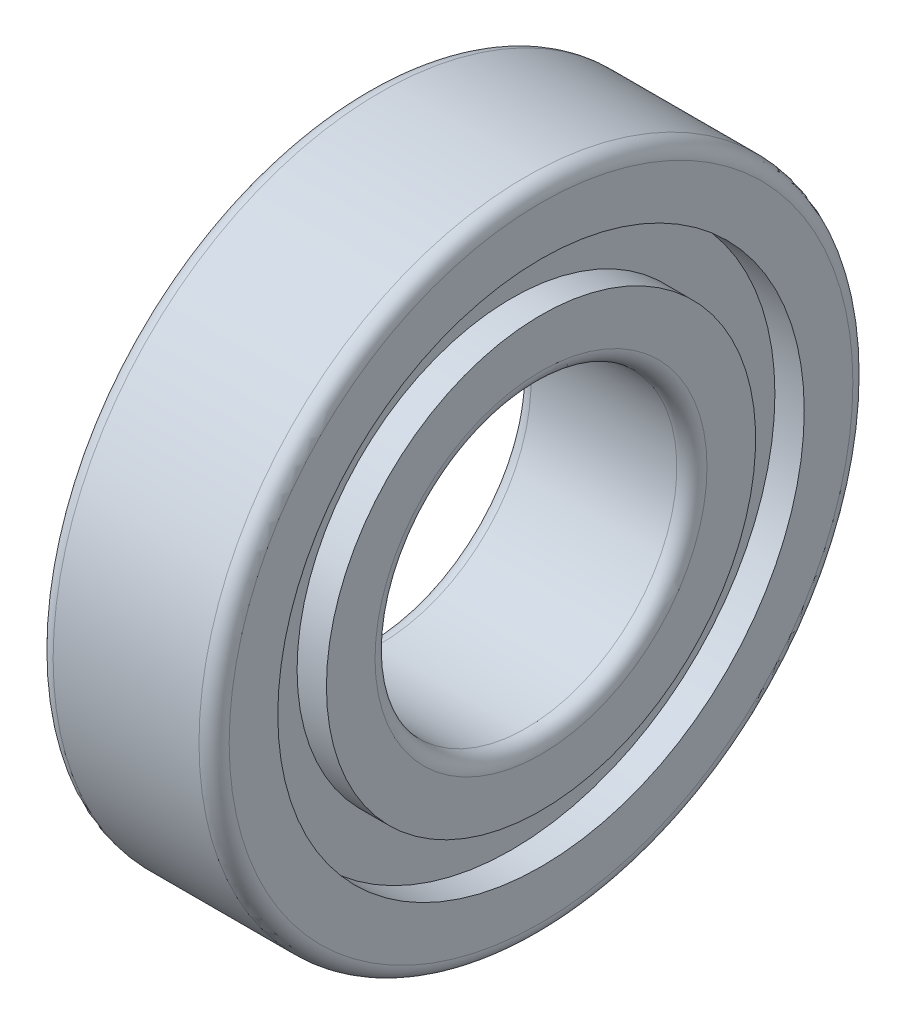
SolidWorks part; units mm, degrees
material "AISI 1020"
ref_plane "Спереди" through (0, 0, 0) normal (0, 0, 1) x (1, 0, 0)
ref_plane "Сверху" through (0, 0, 0) normal (0, 1, 0) x (1, 0, 0)
ref_plane "Справа" through (0, 0, 0) normal (1, 0, 0) x (0, 0, -1)
sketch "Эскиз1" plane through (0, 0, 0) normal (0, 0, 1) x (1, 0, 0)
  line L0 (-1000, 0) -> (49000, 0) construction
  line L1 (0, -1000) -> (0, 49000) construction
  line L2 (1.45, 3) -> (-1.45, 3)
  line L3 (-1.75, 3.3) -> (-1.75, 4.2667)
  line L4 (-1.75, 4.2667) -> (-1.1667, 4.2667)
  line L5 (-1.1667, 4.2667) -> (-1.1667, 5.2333)
  line L6 (-1.1667, 5.2333) -> (-1.75, 5.2333)
  line L7 (-1.75, 5.2333) -> (-1.75, 6.2)
  line L8 (-1.45, 6.5) -> (1.45, 6.5)
  line L9 (1.75, 5.2333) -> (1.75, 6.2)
  line L10 (1.1667, 5.2333) -> (1.75, 5.2333)
  line L11 (1.1667, 4.2667) -> (1.1667, 5.2333)
  line L12 (1.75, 4.2667) -> (1.1667, 4.2667)
  line L13 (1.75, 3.3) -> (1.75, 4.2667)
  arc A0 (-1.45, 3) -> (-1.75, 3.3) centre (-1.45, 3.3) cw
  arc A1 (-1.75, 6.2) -> (-1.45, 6.5) centre (-1.45, 6.2) cw
  arc A2 (1.75, 6.2) -> (1.45, 6.5) centre (1.45, 6.2) ccw
  arc A3 (1.45, 3) -> (1.75, 3.3) centre (1.45, 3.3) ccw
  point P23 (0, 6.5)
  point P27 (0, 3)
  dimension "_r" = 0.3
  dimension "_d" = 6
  dimension "D" = 13
  dimension "B" = 3.5
  dimension "D2" = 2.3333
revolve "Повернуть1" add sketch "Эскиз1" angle 360 about L0
other "PropertyManager" [suppressed]
equation "\"D2@Эскиз1\"= \"B@Эскиз1\" / 3 * 2"
